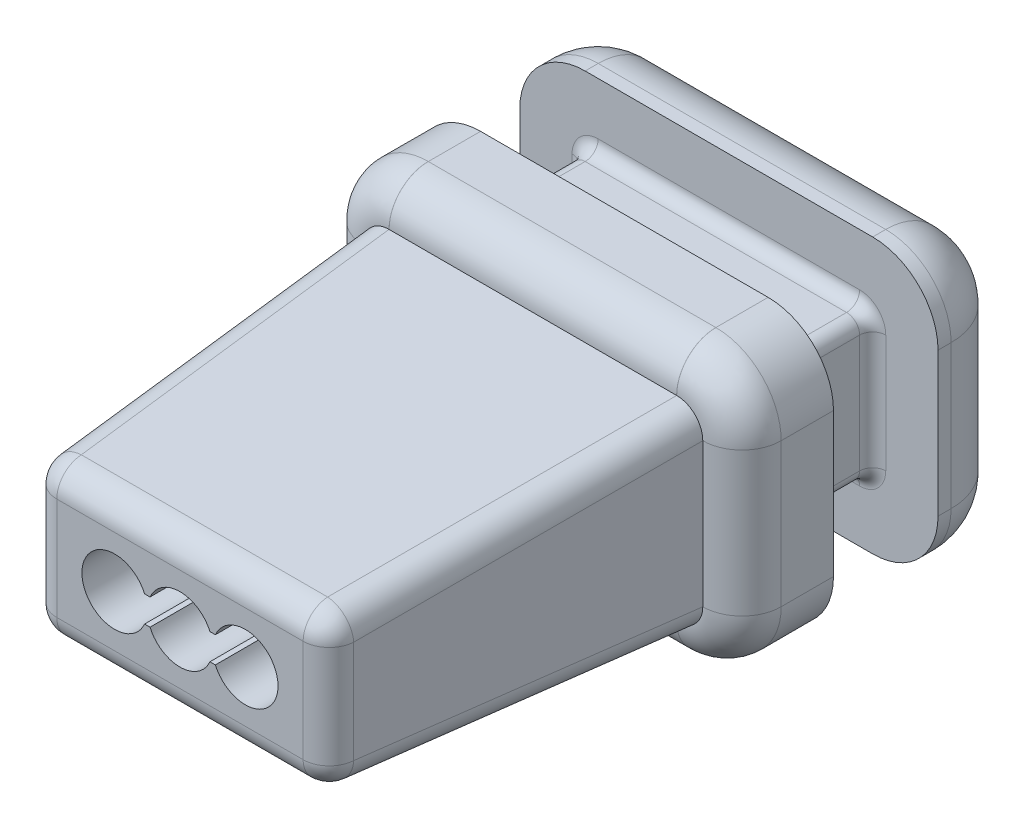
SolidWorks part; units mm, degrees
material "ABS PC"
ref_plane "Front Plane" through (0, 0, 0) normal (0, 0, 1) x (1, 0, 0)
ref_plane "Top Plane" through (0, 0, 0) normal (0, 1, 0) x (1, 0, 0)
ref_plane "Right Plane" through (0, 0, 0) normal (1, 0, 0) x (0, 0, -1)
sketch "Sketch1" plane through (0, 0, 0) normal (0, 0, 1) x (1, 0, 0)
  line L0 (0, 3.4383) -> (0, -2.2617) construction
  line L1 (-2.6, -1.5) -> (2.6, -1.5)
  line L2 (-2.6, -1.5) -> (-2.6, 1.5)
  line L3 (-2.6, 1.5) -> (2.6, 1.5)
  line L4 (2.6, -1.5) -> (2.6, 1.5)
  dimension "D1" = 5.2
  dimension "D2" = 3
  dimension "D3" = 1.5
extrude "Extrude1" add sketch "Sketch1" along normal blind 5.4 draft 3.6
sketch "Sketch2" plane through (0, 0, 0) normal (0, 0, -1) x (-1, 0, 0)
  line L0 (0, 2.2288) -> (0, -4.0317) construction
  line L1 (2.2, -2.1) -> (-2.2, -2.1)
  line L2 (3.2, -1.1) -> (3.2, 1.1)
  line L3 (2.2, 2.1) -> (-2.2, 2.1)
  line L4 (-3.2, -1.1) -> (-3.2, 1.1)
  arc A0 (2.2, 2.1) -> (3.2, 1.1) centre (2.2, 1.1) cw
  arc A1 (2.2, -2.1) -> (3.2, -1.1) centre (2.2, -1.1) ccw
  arc A2 (-2.2, -2.1) -> (-3.2, -1.1) centre (-2.2, -1.1) cw
  arc A3 (-3.2, 1.1) -> (-2.2, 2.1) centre (-2.2, 1.1) cw
  point P9 (3.2, 2.1)
  point P12 (3.2, -2.1)
  point P15 (-3.2, -2.1)
  dimension "D4" = 1
  dimension "D1" = 6.4
  dimension "D2" = 4.2
  dimension "D3" = 2.1
extrude "Extrude2" add sketch "Sketch2" along normal blind 4.2
ref_plane "Plane1" through (0, 0, -1.4) normal (0, 0, 1) x (1, 0, 0)
sketch "Sketch3" plane through (0, 0, -1.4) normal (0, 0, 1) x (1, 0, 0)
  line L0 (0, 2.5571) -> (0, -2.7813) construction
  line L1 (-2.2, 1.1) -> (2.2, 1.1)
  line L2 (-2.2, 1.1) -> (-2.2, -1.1)
  line L3 (-2.2, -1.1) -> (2.2, -1.1)
  line L4 (2.2, 1.1) -> (2.2, -1.1)
  line L6 (3.2, 1.1) -> (3.2, -1.1) construction
  line L8 (2.2, -2.1) -> (-2.2, -2.1) construction
  line L9 (-3.2, -1.1) -> (-3.2, 1.1) construction
  line L10 (-2.2, 2.1) -> (2.2, 2.1) construction
  line L11 (2.2, -2.1) -> (-2.2, -2.1)
  line L12 (-3.2, -1.1) -> (-3.2, 1.1)
  line L13 (-2.2, 2.1) -> (2.2, 2.1)
  line L14 (3.2, 1.1) -> (3.2, -1.1)
  arc A0 (2.2, -2.1) -> (3.2, -1.1) centre (2.2, -1.1) ccw construction
  arc A1 (-3.2, -1.1) -> (-2.2, -2.1) centre (-2.2, -1.1) ccw construction
  arc A2 (-2.2, 2.1) -> (-3.2, 1.1) centre (-2.2, 1.1) ccw construction
  arc A3 (3.2, 1.1) -> (2.2, 2.1) centre (2.2, 1.1) ccw construction
  arc A4 (2.2, -2.1) -> (3.2, -1.1) centre (2.2, -1.1) ccw
  arc A5 (-3.2, -1.1) -> (-2.2, -2.1) centre (-2.2, -1.1) ccw
  arc A6 (-2.2, 2.1) -> (-3.2, 1.1) centre (-2.2, 1.1) ccw
  arc A7 (3.2, 1.1) -> (2.2, 2.1) centre (2.2, 1.1) ccw
extrude "Cut-Extrude1" cut sketch "Sketch3" against normal blind 1.6
sketch "Sketch4" plane through (0, 0, 5.4) normal (0, 0, 1) x (1, 0, 0)
  line L4 (-0.4583, 0.2) -> (-0.5417, 0.2)
  line L5 (-0.5417, -0.2) -> (-0.4583, -0.2)
  line L6 (0.4583, -0.2) -> (0.5417, -0.2)
  line L7 (0.4583, 0.2) -> (0.5417, 0.2)
  arc A4 (0.4583, 0.2) -> (-0.4583, 0.2) centre (0, 0) ccw
  arc A5 (-0.5417, 0.2) -> (-0.5417, -0.2) centre (-1, 0) ccw
  arc A6 (-0.4583, -0.2) -> (0.4583, -0.2) centre (0, 0) ccw
  arc A7 (0.5417, -0.2) -> (0.5417, 0.2) centre (1, 0) ccw
  point P11 (1.0546, -0.1724)
  dimension "D1" = 0.5
  dimension "D2" = 0.5
  dimension "D3" = 0.5
  dimension "D8" = 0.2
  dimension "D4" = 1
  dimension "D5" = 1
  dimension "D6" = 0.4
  dimension "D7" = 0.4
  dimension "D9" = 0.2
  dimension "D10" = 0.0835
  dimension "D11" = 0.0835
  dimension "D12" = 0.0835
extrude "Cut-Extrude2" cut sketch "Sketch4" against normal up to vertex (9.6 mm away) up to point (-3.2, -1.1, -4.2)
fillet "Fillet1" radius 0.4 8 edges at (2.2603, 0, 5.4) (0, -1.1603, 5.4) (-2.2603, 0, 5.4) (0, 1.1603, 5.4) (-2.4301, 1.3301, 2.7) (2.4301, 1.3301, 2.7) (2.4301, -1.3301, 2.7) (-2.4301, -1.3301, 2.7)
fillet "Fillet2" radius 0.6 4 edges at (0, 2.1, 0) (-3.2, 0, 0) (3.2, 0, 0) (0, -2.1, 0)
fillet "Fillet3" radius 1 8 edges at (2.9071, -1.8071, -4.2) (3.2, 0, -4.2) (2.9071, 1.8071, -4.2) (0, 2.1, -4.2) (-2.9071, 1.8071, -4.2) (-3.2, 0, -4.2) (-2.9071, -1.8071, -4.2) (0, -2.1, -4.2)
fillet "Fillet4" radius 0.2 12 edges at (0, 1.1, -3) (2.2, 0, -3) (-2.2, 0, -3) (-2.2, 1.1, -2.2) (2.2, 1.1, -2.2) (2.2, -1.1, -2.2) (0, -1.1, -3) (-2.2, -1.1, -2.2) (0, -1.1, -1.4) (2.2, 0, -1.4) (-2.2, 0, -1.4) (0, 1.1, -1.4)
ref_axis "Axis1" through (0, 0, 6.5451) along (0, 0, -1)
